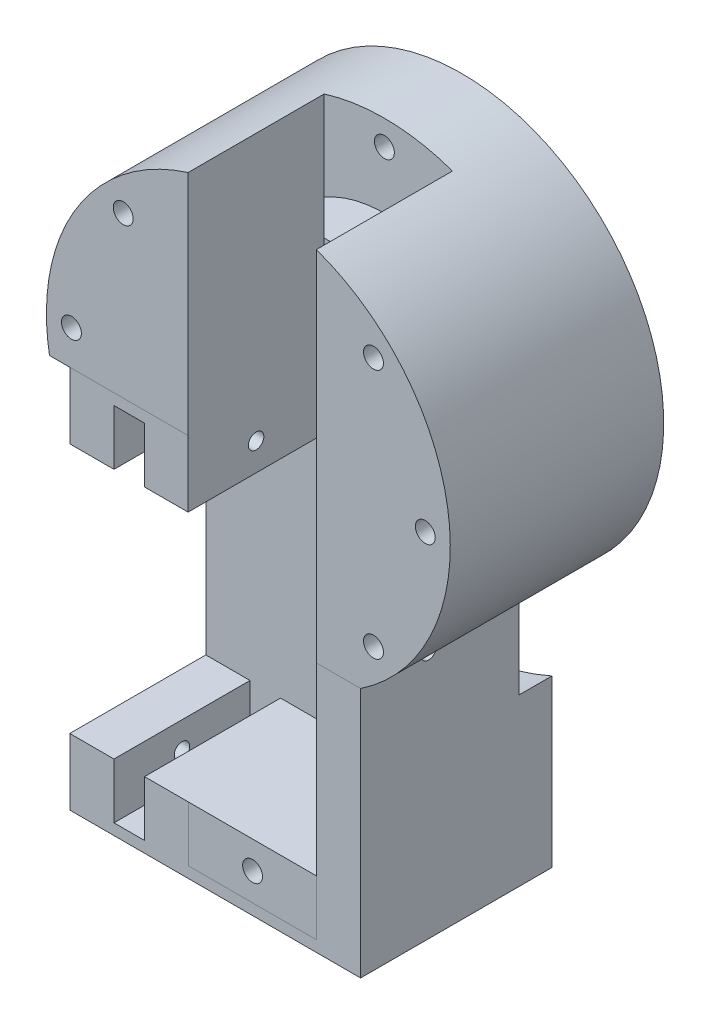
SolidWorks part; units mm, degrees
ref_plane "Plan de face" through (0, 0, 0) normal (0, 0, 1) x (1, 0, 0)
ref_plane "Plan de dessus" through (0, 0, 0) normal (0, 1, 0) x (1, 0, 0)
ref_plane "Plan de droite" through (0, 0, 0) normal (1, 0, 0) x (0, 0, -1)
sketch "Esquisse1" plane through (0, 0, 0) normal (0, 0, 1) x (1, 0, 0)
  line L0 (-6.15, 0) -> (-6.15, -6.15) construction
  line L1 (0, 0) -> (-22.3, 0)
  line L2 (0, 0) -> (0, -43)
  line L3 (0, -43) -> (-22.3, -43)
  line L4 (-22.3, 0) -> (-22.3, -43)
  line L5 (-6.15, -6.15) -> (0, -6.15) construction
  circle A0 centre (-6.15, -6.15) radius 2.45
  dimension "D1" = 22.3
  dimension "D2" = 43
  dimension "D3" = 6.15
  dimension "D4" = 6.15
extrude "Boss.-Extru.1" add sketch "Esquisse1" along normal blind 5
sketch "Esquisse2" plane through (0, 0, 5) normal (0, 0, 1) x (1, 0, 0)
  circle A0 centre (-6.15, -6.15) radius 2.45
  circle A1 centre (-6.15, -6.15) radius 0.7
extrude "Boss.-Extru.2" add sketch "Esquisse2" against normal blind 2.47
sketch "Esquisse3" plane through (0, 0, 5) normal (0, 0, 1) x (1, 0, 0)
  line L0 (-22.3, 0) -> (-22.3, -43) construction
  line L1 (-22.3, -38) -> (-18.3, -38)
  line L2 (-22.3, -38) -> (-22.3, -43)
  line L3 (-22.3, -43) -> (-18.3, -43)
  line L4 (-18.3, -38) -> (-18.3, -43)
  line L5 (-22.3, -43) -> (0, -43) construction
  line L6 (-18.3, -38) -> (-18.3, 0) construction
  line L7 (-15.54, -43) -> (-11.54, -43)
  line L8 (-15.54, -43) -> (-15.54, -38)
  line L9 (-15.54, -38) -> (-11.54, -38)
  line L10 (-11.54, -43) -> (-11.54, -38)
  line L11 (0, 0) -> (-22.3, 0) construction
  line L12 (-15.54, -38) -> (-15.54, 0) construction
  line L13 (-22.3, -15.32) -> (-18.3, -15.32)
  line L14 (-22.3, -15.32) -> (-22.3, -10.32)
  line L15 (-22.3, -10.32) -> (-18.3, -10.32)
  line L16 (-18.3, -15.32) -> (-18.3, -10.32)
  line L17 (-18.3, -15.32) -> (0, -15.32) construction
  line L18 (0, -43) -> (0, 0) construction
  line L19 (-18.3, -10.32) -> (0, -10.32) construction
  line L20 (-15.54, -15.32) -> (-11.6, -15.32)
  line L21 (-15.54, -15.32) -> (-15.54, -10.32)
  line L22 (-15.54, -10.32) -> (-11.6, -10.32)
  line L23 (-11.6, -15.32) -> (-11.6, -10.32)
  line L24 (-18.3, -38) -> (0, -38) construction
  dimension "D1" = 4
  dimension "D2" = 5
  dimension "D3" = 4
  dimension "D4" = 2.76
  dimension "D5" = 22.68
  dimension "D6" = 5
extrude "Boss.-Extru.3" add sketch "Esquisse3" along normal blind 12.3
sketch "Esquisse4" plane through (-22.3, 0, 0) normal (-1, 0, 0) x (0, 0, 1)
  line L0 (5, -10.32) -> (5, -15.32) construction
  line L1 (17.3, -15.32) -> (5, -15.32) construction
  line L2 (5, -15.32) -> (5, -38) construction
  line L3 (5, -38) -> (5, -43) construction
  line L4 (17.3, -43) -> (0, -43) construction
  line L5 (5, -12.82) -> (17.3, -12.82) construction
  line L6 (17.3, -10.32) -> (17.3, -15.32) construction
  line L7 (11.15, -38) -> (11.15, -43) construction
  line L9 (17.3, -38) -> (5, -38) construction
  circle A0 centre (11.15, -12.82) radius 0.7
  circle A1 centre (11.15, -40.42) radius 0.7
  dimension "D1" = 27.6
extrude "Enlèv. mat.-Extru.1" cut sketch "Esquisse4" against normal through all
sketch "Esquisse5" plane through (0, -43, 0) normal (0, -1, 0) x (1, 0, 0)
  line L0 (-22.3, 17.3) -> (-11.54, 17.3)
  line L2 (0, 5) -> (0, 0)
  line L3 (0, 0) -> (-22.3, 0)
  line L4 (-22.3, 0) -> (-22.3, 17.3)
  line L5 (-11.54, 17.3) -> (0, 17.3)
  line L6 (0, 17.3) -> (0, 5)
extrude "Boss.-Extru.4" add sketch "Esquisse5" along normal blind 1
sketch "Esquisse6" plane through (0, -10.32, 0) normal (0, 1, 0) x (1, 0, 0)
  line L0 (-22.3, -5) -> (-22.3, -17.3)
  line L1 (-22.3, -17.3) -> (-11.6, -17.3)
  line L3 (-11.6, -5) -> (-22.3, -5)
  line L5 (-11.6, -5) -> (-11.6, -17.3)
extrude "Boss.-Extru.5" add sketch "Esquisse6" along normal blind 1
sketch "Esquisse7" plane through (0, 0, 0) normal (1, 0, 0) x (0, 0, -1)
  line L0 (0, -21.47) -> (-11.15, -21.47) construction
  line L1 (0, -44) -> (0, 0) construction
  line L2 (-5, -9.32) -> (0, -9.32)
  line L3 (-5, -15.32) -> (0, -15.32) construction
  line L4 (0, -27.62) -> (-5, -27.62) construction
  line L5 (-5, -43) -> (-5, 0) construction
  line L6 (-11.15, -21.47) -> (-11.15, -15.32) construction
  line L8 (0, -15.32) -> (0, -27.62)
  line L10 (0, -9.32) -> (0, -15.32)
  line L11 (-5, -9.32) -> (-17.3, -9.32)
  line L12 (-17.3, -9.32) -> (-17.3, -44)
  line L13 (-17.3, -44) -> (0, -44)
  line L14 (0, -44) -> (0, -27.62)
  circle A1 centre (-11.15, -21.47) radius 0.7
  dimension "D1" = 6.15
  dimension "D2" = 11.15
  dimension "D3" = 6.15
extrude "Boss.-Extru.6" add sketch "Esquisse7" along normal blind 4
sketch "Esquisse10" plane through (0, 0, 0) normal (0, 0, -1) x (-1, 0, 0)
  circle A0 centre (6.15, -6.15) radius 10.8159
  circle A1 centre (6.15, -6.15) radius 18.2589
extrude "Boss.-Extru.7" add sketch "Esquisse10" along normal blind 2 and the other way blind 5
sketch "Esquisse11" plane through (0, 0, 0) normal (0, 0, -1) x (-1, 0, 0)
  circle A0 centre (6.15, -6.15) radius 18.2589
  circle A1 centre (6.15, -6.15) radius 25
extrude "Enlèv. mat.-Extru.4" cut sketch "Esquisse11" against normal blind 3
sketch "Esquisse13" plane through (0, 0, 5) normal (0, 0, 1) x (1, 0, 0)
  line L1 (-11.54, -38) -> (0, -38)
  line L2 (-11.54, -38) -> (-11.54, -43)
  line L3 (-11.54, -43) -> (0, -43)
  line L4 (0, -38) -> (0, -43)
extrude "Boss.-Extru.14" add sketch "Esquisse13" along normal through all
sketch "Esquisse14" plane through (0, 0, 5) normal (0, 0, 1) x (1, 0, 0)
  line L0 (-11.6, 11.2765) -> (-11.6, -9.32)
  line L1 (-11.6, -9.32) -> (-24.1316, -9.32)
  arc A0 (4, -21.3278) -> (-22.3, -14.6685) centre (-6.15, -6.15) ccw construction
  arc A1 (-24.1316, -9.32) -> (-11.6, 11.2765) centre (-6.15, -6.15) cw
extrude "Boss.-Extru.15" add sketch "Esquisse14" along normal through all
sketch "Esquisse15" plane through (0, 0, 5) normal (0, 0, 1) x (1, 0, 0)
  line L0 (0, 11.042) -> (0, -21.3278)
  line L1 (0, -9.32) -> (0, -38) construction
  line L2 (0, -21.3278) -> (4, -21.3278)
  line L4 (4, -9.32) -> (4, -24.9699) construction
  line L5 (4, -9.32) -> (4, -44) construction
  arc A0 (0, 11.042) -> (4, -21.3278) centre (-6.15, -6.15) cw
  arc A1 (4, -21.3278) -> (-11.6, 11.2765) centre (-6.15, -6.15) ccw construction
extrude "Boss.-Extru.19" add sketch "Esquisse15" along normal through all and the other way blind 1
sketch "Esquisse16" plane through (0, 0, 17.3002) normal (0, 0, 1) x (1, 0, 0)
  line L0 (-22.3, -14.6685) -> (-22.3, -44) construction
  line L1 (-22.3, -44) -> (4, -44) construction
  line L2 (4, -44) -> (4, -21.3278) construction
  arc A0 (4, -21.3278) -> (-22.3, -14.6685) centre (-6.15, -6.15) ccw construction
  circle A1 centre (-6.15, -6.15) radius 16 construction
  circle A2 centre (9.85, -6.15) radius 0.9
  circle A3 centre (5.1637, -17.4637) radius 0.9
  circle A4 centre (-6.15, -22.15) radius 0.9 construction
  circle A5 centre (-17.4637, -17.4637) radius 0.9 construction
  circle A6 centre (-22.15, -6.15) radius 0.9
  circle A7 centre (-17.4637, 5.1637) radius 0.9
  circle A8 centre (-6.15, 9.85) radius 0.9
  circle A9 centre (5.1637, 5.1637) radius 0.9
  point P30 (-6.15, -6.15)
  dimension "D1" = 8
extrude "Enlèv. mat.-Extru.5" cut sketch "Esquisse16" against normal through all
sketch "Esquisse17" plane through (0, 0, 17.3001) normal (0, 0, 1) x (1, 0, 0)
  line L0 (-11.54, -40.5) -> (0, -40.5) construction
  line L1 (-11.54, -43) -> (-11.54, -38) construction
  line L2 (0, -38) -> (0, -43) construction
  circle A0 centre (-5.77, -40.5) radius 0.9
extrude "Enlèv. mat.-Extru.6" cut sketch "Esquisse17" against normal through all
